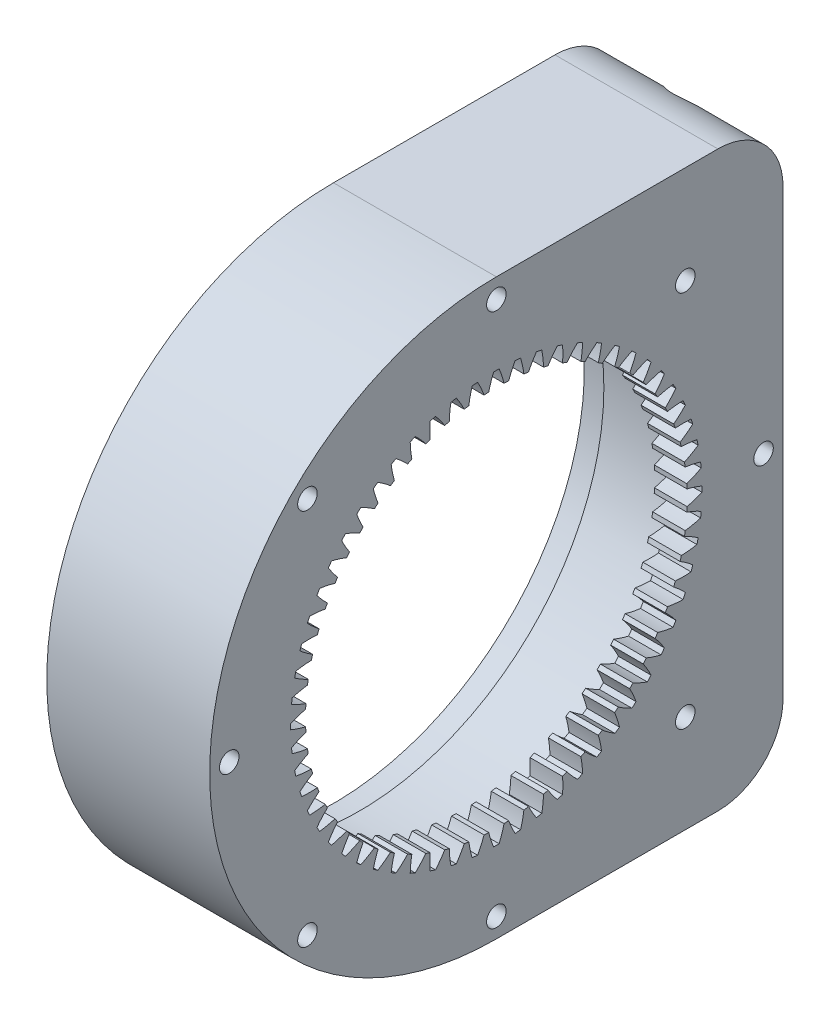
SolidWorks part; units mm, degrees
ref_plane "Plane1" through (0, 0, 0) normal (0, 0, 1) x (1, 0, 0)
ref_plane "Plane2" through (0, 0, 0) normal (0, 1, 0) x (1, 0, 0)
ref_plane "Plane3" through (0, 0, 0) normal (1, 0, 0) x (0, 0, -1)
other "Configuration Table"
sketch "HoldingSke" plane through (0, 0, 0) normal (0, 1, 0) x (1, 0, 0)
  line L0 (0, 0) -> (0.495, -0.8575)
  line L1 (-15, 0) -> (100, 0) construction
  line L2 (0, 0) -> (-2.1039, 2.3779)
  line L3 (0, 0) -> (-11.863, 4.5341)
  line L4 (0, 0) -> (4.318, 7.479)
  line L5 (0, 0) -> (-23.7986, -8.8762)
  line L6 (0, 0) -> (-10.5278, -7.1032)
  line L7 (-2.1039, 2.3779) -> (3.3635, 27.1825)
  line L8 (-76.2, 3.3879) -> (-54.61, 3.3879)
  line L9 (-67.7845, 28.3722) -> (-49.3413, 33.142)
  line L10 (-76.2, 71.12) -> (104.1128, 71.12)
  line L11 (0, 0) -> (-5, 0)
  line L12 (-76.2, 101.6) -> (-76.162, 101.6)
  line L13 (24.9733, 27.94) -> (52.9518, 28.4284)
  line L14 (24.9733, 27.94) -> (24.9743, 27.94)
  line L15 (24.9733, 27.94) -> (100.4006, 29.5858)
  circle A0 centre (0, 0) radius 44
  circle A1 centre (0, 0) radius 12.7
  circle A2 centre (0, 0) radius 12.7
  dimension "Num_teeth" = 60
  dimension "Pitch_radius" = 180.3128
  dimension "Width" = 5
  dimension "Diameter" = 88
sketch "BasProSke" plane through (0, 0, 0) normal (0, 1, 0) x (1, 0, 0)
  line L0 (-10, 0) -> (60, 0) construction
  line L1 (0, 29.29) -> (0, 44)
  line L2 (0, 29.29) -> (5, 29.29)
  line L3 (5, 29.29) -> (5, 44)
  line L4 (5, 44) -> (0, 44)
  dimension "Thickness" = 5
  dimension "Diameter" = 88
revolve "Base-Revolve" add sketch "BasProSke" angle 360 about L0
sketch "TooCutSke" plane through (0, 0, 0) normal (1, 0, 0) x (0, 0, -1)
  line L3 (0.8882, 30.287) -> (0.8882, 53.6633) construction
  line L4 (0, 0) -> (0, 59.563) construction
  line L5 (0, 0) -> (-3.576, 68.2339) construction
  line L6 (-13.5593, 25.727) -> (36.4092, 28.3457) construction
  circle A0 centre (0, 0) radius 30.3 construction
  circle A1 centre (0, 0) radius 31.5635 construction
  circle A2 centre (0, 0) radius 26.4014 construction
  circle A3 centre (0, 0) radius 29.2646 construction
  arc A4 (1.1776, 29.2409) -> (0.4225, 31.5607) centre (-13.5593, 25.727) ccw
  arc A5 (1.1776, 29.2409) -> (-1.1776, 29.2409) centre (0, 0) ccw
  arc A6 (0.4225, 31.5607) -> (-0.4225, 31.5607) centre (0, 0) ccw
  arc A7 (-0.4225, 31.5607) -> (-1.1776, 29.2409) centre (13.5593, 25.727) ccw
extrude "ToothCut" cut sketch "TooCutSke" along normal through all
fillet "Breaks" [suppressed] radius 0.101
fillet "RootFillets" [suppressed] radius 0.2535
pattern_circular "TeethCuts" count 60 every 6 about axis through (-10, 0, 0) along (1, 0, 0) of "RootFillets", "Breaks", "ToothCut"
sketch "Sketch4" plane through (0, 0, 0) normal (-1, 0, 0) x (0, 0, 1)
  circle A0 centre (0, 0) radius 44
  circle A1 centre (0, 0) radius 38.5
  circle A2 centre (0, 0) radius 44 construction
  dimension "D1" = 77
extrude "Boss-Extrude3" add sketch "Sketch4" along normal blind 20
sketch "Sketch7" plane through (5, 0, 0) normal (1, 0, 0) x (0, 0, -1)
  line L0 (0, 44) -> (44, 44)
  line L1 (44, 44) -> (44, 0)
  circle A0 centre (0, 0) radius 44 construction
  arc A1 (44, 0) -> (0, 44) centre (0, 0) ccw
extrude "Boss-Extrude5" add sketch "Sketch7" against normal up to surface (25 mm away) up to face at (-20, 0, 44)
sketch "Sketch10" plane through (5, 0, 0) normal (1, 0, 0) x (0, 0, -1)
  line L0 (0, -44) -> (44, -44)
  line L1 (44, -44) -> (44, 0)
  line L2 (44, 0) -> (44, 44) construction
  circle A0 centre (0, 0) radius 44 construction
  arc A1 (0, -44) -> (44, 0) centre (0, 0) ccw
  dimension "D1" = 180
extrude "Boss-Extrude6" add sketch "Sketch10" against normal up to surface (25 mm away) up to face at (-20, 11.6291, -11.6291)
fillet "Fillet1" radius 10 2 edges at (-7.5, 44, -44) (-7.5, -44, -44)
sketch "Sketch14" plane through (0, 0, 0) normal (-1, 0, 0) x (0, 0, 1)
  circle A0 centre (0, 0) radius 37.5
  circle A1 centre (0, 0) radius 38.5 construction
  circle A2 centre (0, 0) radius 38.5
  dimension "D1" = 1
extrude "Boss-Extrude7" add sketch "Sketch14" along normal blind 16
sketch "Sketch15" plane through (-20, 0, 0) normal (-1, 0, 0) x (0, 0, 1)
  circle A0 centre (-41, 0) radius 1.5
  point P3 (0, 0)
  dimension "D1" = 3
  dimension "D2" = 41
extrude "Cut-Extrude1" cut sketch "Sketch15" against normal through all
pattern_circular "CirPattern1" count 8 over 360 about axis through (-16, 0, 0) along (1, 0, 0) of "Cut-Extrude1" reverse direction yes
sketch "Sketch16" plane through (0, 0, -44) normal (0, 0, -1) x (-1, 0, 0)
  line L0 (-5, 44) -> (20, 44) construction
  line L1 (20, -44) -> (-5, -44) construction
  line L2 (7.5, -956) -> (7.5, 49044) construction
  circle A0 centre (7.5, 38) radius 4.25
  circle A1 centre (7.5, -38) radius 4.25
  point P8 (7.5, 44)
  dimension "D1" = 6
  dimension "D2" = 8.5
  dimension "D3" = 6
extrude "Cut-Extrude2" cut sketch "Sketch16" against normal blind 20
equation "' \"Module@HoldingSke\" = 6.35"
equation "' \"Num_teeth@HoldingSke\" = 24"
equation "' \"Ap@HoldingSke\" =  14.5"
equation "' \"Ap@HoldingSke\" = 14.5"
equation "' \"Width@HoldingSke\" = 12"
equation "' \"Diameter@HoldingSke\" = 8 * 25.4"
equation "' \"Show_teeth@HoldingSke\" = 100"
equation "' \"Backlash@HoldingSke\" = 0.009 * 25.4"
equation "' \"Addendum_fac@HoldingSke\" = 1.0"
equation "' \"Dedendum_fac@HoldingSke\" = 1.25"
equation "' \"Dedendum_add@HoldingSke\" = 0.00005 * 25.4"
equation "' \"Clearance_fac@HoldingSke\" = 0.25"
equation "\"Pitch@HoldingSke\" = 1 / \"Module@HoldingSke\" "
equation "\"Overcut_dia@TooCutSke\" = (\"Num_teeth@HoldingSke\" - 2 * \"Addendum_fac@HoldingSke\") / \"Pitch@HoldingSke\" - 0.002 * 25.4"
equation "\"Pitch_dia@TooCutSke\" = \"Num_teeth@HoldingSke\" / \"Pitch@HoldingSke\""
equation "\"Base_dia@TooCutSke\" = \"Num_teeth@HoldingSke\" / \"Pitch@HoldingSke\" * cos((\"Ap@HoldingSke\"  * 3.14159265 / 180)) * 0.90"
equation "\"Root_dia@TooCutSke\" = \"Num_teeth@HoldingSke\"  / \"Pitch@HoldingSke\" + 2 *  \"Dedendum_fac@HoldingSke\"/ \"Pitch@HoldingSke\" + \"Dedendum_add@HoldingSke\" * 2"
equation "\"Half_ang@TooCutSke\" = 180 / \"Num_teeth@HoldingSke\""
equation "\"Half_CT@TooCutSke\" = \"Num_teeth@HoldingSke\" / \"Pitch@HoldingSke\" * sin((3.14159265 / 2 / \"Num_teeth@HoldingSke\")) / 2 + 10 * \"Backlash@HoldingSke\" / 4"
equation "\"Flank_rad@TooCutSke\" = \"Num_teeth@HoldingSke\" / \"Pitch@HoldingSke\" / 4"
equation "\"Radius@RootFillets\"= \"Clearance_fac@HoldingSke\" / \"Pitch@HoldingSke\" + \"Dedendum_add@HoldingSke\""
equation "\"Break_rad@Breaks\" = 0.02 / \"Pitch@HoldingSke\" * 5"
equation "\"Num_teeth@TeethCuts\" = int( \"Show_teeth@HoldingSke\" ) + 1"
equation "\"Num_teeth@TeethCuts\" = ((sgn( \"Num_teeth@TeethCuts\" - \"Num_teeth@HoldingSke\" )-1)*( \"Num_teeth@TeethCuts\" - \"Num_teeth@HoldingSke\" ))/-2+ \"Num_teeth@HoldingSke\""
equation "\"Num_teeth@TeethCuts\" = ((sgn( \"Num_teeth@TeethCuts\" - 2.0)+1)*( \"Num_teeth@TeethCuts\" - 2.0))/2 +2.0"
equation "\"Angle@TeethCuts\" = 360.0 / \"Num_teeth@HoldingSke\""
equation "\"Diameter@BasProSke\" = \"Num_teeth@HoldingSke\"  / \"Pitch@HoldingSke\" + 2 *  \"Dedendum_fac@HoldingSke\"/ \"Pitch@HoldingSke\" + \"Dedendum_add@HoldingSke\" * 2 + 0.002 * 25.4"
equation "\"Diameter@BasProSke\" = ((sgn( \"Diameter@BasProSke\"  - \"Diameter@HoldingSke\" )+1)*( \"Diameter@BasProSke\"  - \"Diameter@HoldingSke\" ))/2 + \"Diameter@HoldingSke\""
equation "\"Inside_diameter@BasProSke\" =  (\"Num_teeth@HoldingSke\" - 2 * \"Addendum_fac@HoldingSke\") / \"Pitch@HoldingSke\" "
equation "\"Thickness@BasProSke\"  = \"Width@HoldingSke\""
